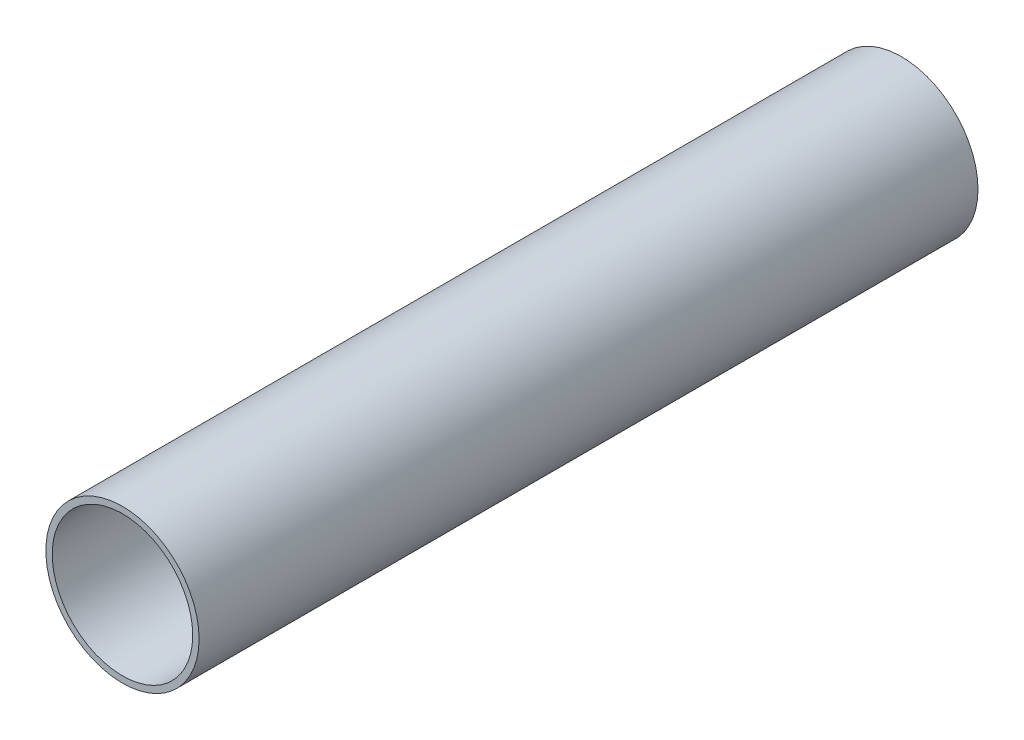
SolidWorks part; units mm, degrees
ref_plane "Front Plane" through (0, 0, 0) normal (0, 0, 1) x (1, 0, 0)
ref_plane "Top Plane" through (0, 0, 0) normal (0, 1, 0) x (1, 0, 0)
ref_plane "Right Plane" through (0, 0, 0) normal (1, 0, 0) x (0, 0, -1)
sketch "Sketch1" plane through (0, 0, 0) normal (0, 0, 1) x (1, 0, 0)
  circle A0 centre (0, 0) radius 63.5
  circle A1 centre (0, 0) radius 69.85
  circle A2 centre (0, 0) radius 76.2
  dimension "D1" = 152.4
  dimension "D2" = 139.7
  dimension "D3" = 127
extrude "Boss-Extrude1" add sketch "Sketch1" along normal blind 762 contours A2 A1 region at (-74.0447, 0, 0)
extrude "Boss-Extrude2" add sketch "Sketch1<3>" against normal blind 12.7 contours A1 A0 | A2 A1 region at (-67.8743, 0, 0) region at (-74.0447, 0, 0)
sketch "Sketch1<3>" plane through (0, 0, 0) normal (0, 0, 1) x (1, 0, 0) same geometry as "Sketch1"
